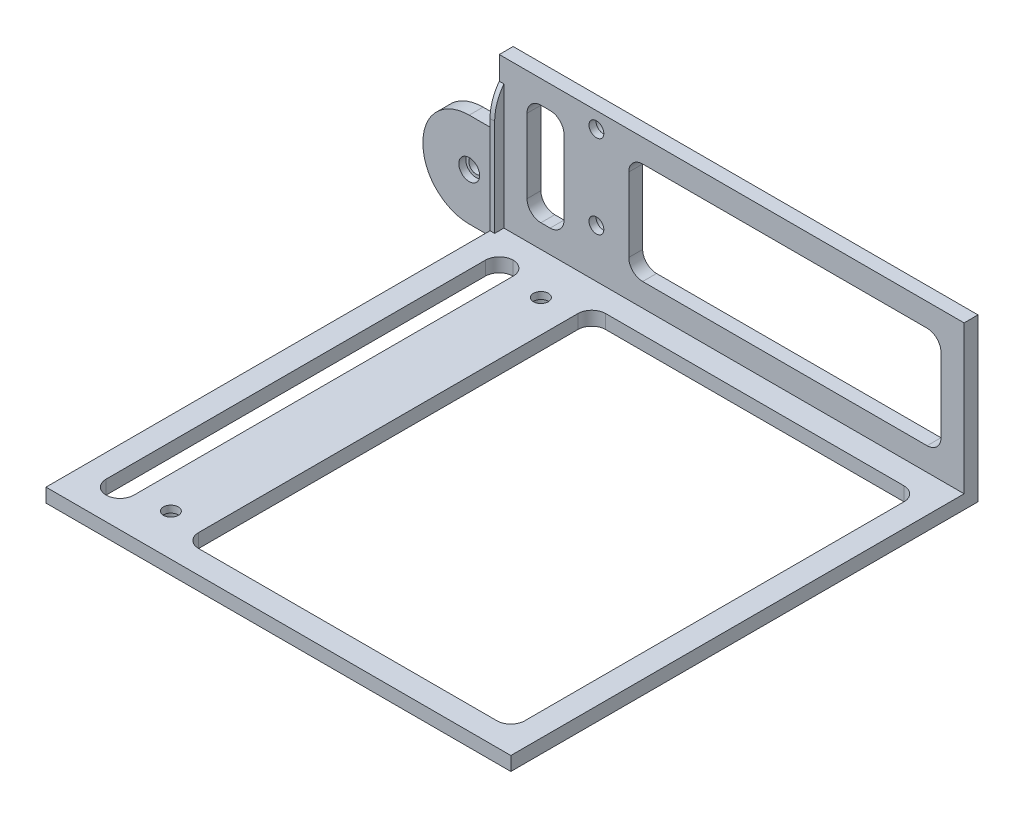
SolidWorks part; units mm, degrees
ref_plane "Front Plane" through (0, 0, 0) normal (0, 0, 1) x (1, 0, 0)
ref_plane "Top Plane" through (0, 0, 0) normal (0, 1, 0) x (1, 0, 0)
ref_plane "Right Plane" through (0, 0, 0) normal (1, 0, 0) x (0, 0, -1)
sketch "Sketch1" plane through (0, 0, 0) normal (0, 0, 1) x (1, 0, 0)
  line L1 (0, 0) -> (117, 0)
  line L2 (0, 0) -> (0, 35)
  line L3 (0, 35) -> (117, 35)
  line L4 (117, 0) -> (117, 35)
  line L5 (16.5, 30) -> (17.5, 30)
  line L6 (16.5, 30) -> (16.5, 3)
  line L7 (16.5, 3) -> (17.5, 3)
  line L8 (17.5, 30) -> (17.5, 3)
  line L9 (0, 0) -> (117, 0)
  line L10 (0, 0) -> (0, 3)
  line L11 (0, 3) -> (117, 3)
  line L12 (117, 0) -> (117, 3)
  circle A0 centre (10, 10.2) radius 1.6
  circle A2 centre (37.5, 13.5) radius 1.6
  circle A3 centre (37.5, 31.5) radius 1.6
  dimension "D3" = 10.2
  dimension "D4" = 3.2
  dimension "D6" = 1
  dimension "D7" = 3
  dimension "D8" = 5
  dimension "D10" = 13.5
  dimension "D11" = 3.2
  dimension "D12" = 3.2
  dimension "D1" = 117
  dimension "D2" = 35
  dimension "D5" = 10
  dimension "D9" = 99.5
  dimension "D13" = 20
  dimension "D14" = 20
  dimension "D15" = 18
  dimension "D16" = 3
extrude "Boss-Extrude1" add sketch "Sketch1" along normal blind 3 contours L2 L11 L6 L5 L8 L4 L3 A3 A2 A0 | L11 L2 L1 L4 L7 | L6 L7 L8 L5 region at (58.5, 1.5, 0) region at (59.0005, 19.0222, 0)
extrude "Boss-Extrude2" add sketch "Sketch1<3>" along normal blind 5 contours L6 L7 L8 L5
sketch "Sketch1<3>" plane through (0, 0, 0) normal (0, 0, 1) x (1, 0, 0) same geometry as "Sketch1"
extrude "Boss-Extrude3" add sketch "Sketch1<7>" along normal blind 101 contours L11 L2 L1 L4 L7 region at (58.5, 1.5, 0)
sketch "Sketch1<7>" plane through (0, 0, 0) normal (0, 0, 1) x (1, 0, 0) same geometry as "Sketch1"
sketch "Sketch2" plane through (0, 0, 0) normal (0, 0, -1) x (-1, 0, 0)
  circle A0 centre (-37.5, 31.5) radius 2.25
  circle A1 centre (-37.5, 13.5) radius 2.25
  dimension "D1" = 4.5
  dimension "D2" = 4.5
extrude "Cut-Extrude1" cut sketch "Sketch2" against normal blind 1.5
sketch "Sketch4" plane through (0, 0, 3) normal (0, 0, 1) x (1, 0, 0)
  circle A0 centre (10, 10.2) radius 2.25
  dimension "D1" = 4.5
extrude "Cut-Extrude2" cut sketch "Sketch4" against normal blind 1.5
sketch "Sketch5" plane through (0, 3, 0) normal (0, 1, 0) x (1, 0, 0)
  line L0 (117, -3) -> (17.5, -3) construction
  line L1 (17.5, -5) -> (17.5, -3) construction
  circle A0 centre (34.5, -12) radius 1.6
  circle A1 centre (34.5, -92) radius 1.6
  dimension "D1" = 9
  dimension "D2" = 3.2
  dimension "D4" = 3.2
  dimension "D3" = 17
  dimension "D5" = 80
  dimension "D6" = 17
extrude "Cut-Extrude3" cut sketch "Sketch5" against normal blind 3
sketch "Sketch6" plane through (0, 0, 0) normal (0, -1, 0) x (1, 0, 0)
  circle A0 centre (34.5, 92) radius 2.25
  circle A1 centre (34.5, 12) radius 2.25
  dimension "D1" = 4.5
  dimension "D2" = 4.5
extrude "Cut-Extrude4" cut sketch "Sketch6" against normal blind 1.5
sketch "Sketch7" plane through (0, 3, 0) normal (0, 1, 0) x (1, 0, 0)
  line L1 (0, -101) -> (16.5, -101)
  line L2 (0, -101) -> (0, -3)
  line L3 (0, -3) -> (16.5, -3)
  line L4 (16.5, -101) -> (16.5, -3)
extrude "Cut-Extrude5" cut sketch "Sketch7" against normal blind 3
sketch "Sketch8" plane through (0, 0, 3) normal (0, 0, 1) x (1, 0, 0)
  line L0 (16.5, 0) -> (16.5, 30) construction
  line L1 (16.5, 20.4) -> (0, 20.4)
  line L2 (16.5, 20.4) -> (16.5, 35)
  line L3 (16.5, 35) -> (0, 35)
  line L4 (0, 20.4) -> (0, 35)
  circle A0 centre (10, 10.2) radius 2.25 construction
  dimension "D1" = 10.2
extrude "Cut-Extrude6" cut sketch "Sketch8" against normal blind 3
fillet "Fillet1" radius 10 1 edges at (0, 20.4, 1.5)
fillet "Fillet2" radius 10 1 edges at (0, 0, 1.5)
fillet "Fillet3" radius 10 1 edges at (17, 30, 5)
sketch "Sketch9" plane through (0, 0, 3) normal (0, 0, 1) x (1, 0, 0)
  line L0 (16.5, 35) -> (117, 35) construction
  line L1 (44.5, 30) -> (112, 30)
  line L2 (44.5, 30) -> (44.5, 8)
  line L3 (44.5, 8) -> (112, 8)
  line L4 (112, 30) -> (112, 8)
  line L5 (117, 3) -> (117, 35) construction
  line L6 (117, 3) -> (17.5, 3) construction
  line L7 (16.5, 35) -> (117, 35) construction
  line L8 (22.5, 30) -> (30.5, 30)
  line L9 (22.5, 30) -> (22.5, 8)
  line L10 (22.5, 8) -> (30.5, 8)
  line L11 (30.5, 30) -> (30.5, 8)
  line L12 (17.5, 3) -> (17.5, 30) construction
  circle A0 centre (37.5, 13.5) radius 1.6 construction
  circle A1 centre (37.5, 31.5) radius 1.6 construction
  dimension "D1" = 5
  dimension "D2" = 5
  dimension "D3" = 5
  dimension "D4" = 7
  dimension "D5" = 5
  dimension "D6" = 5
  dimension "D7" = 7
  dimension "D8" = 5
extrude "Cut-Extrude7" cut sketch "Sketch9" against normal blind 10
fillet "Fillet4" radius 3 8 edges at (44.5, 30, 1.5) (44.5, 8, 1.5) (112, 8, 1.5) (112, 30, 1.5) (22.5, 8, 1.5) (30.5, 8, 1.5) (22.5, 30, 1.5) (30.5, 30, 1.5)
sketch "Sketch10" plane through (0, 3, 0) normal (0, 1, 0) x (1, 0, 0)
  line L0 (117, -3) -> (17.5, -3) construction
  line L1 (41.5, -8) -> (112, -8)
  line L2 (41.5, -8) -> (41.5, -96)
  line L3 (41.5, -96) -> (112, -96)
  line L4 (112, -8) -> (112, -96)
  line L5 (21.5, -8) -> (27.5, -8)
  line L6 (21.5, -8) -> (21.5, -96)
  line L7 (21.5, -96) -> (27.5, -96)
  line L8 (27.5, -8) -> (27.5, -96)
  line L9 (117, -101) -> (117, -3) construction
  line L10 (16.5, -101) -> (117, -101) construction
  line L11 (16.5, -101) -> (16.5, -5) construction
  circle A0 centre (34.5, -12) radius 1.6 construction
  dimension "D7" = 7
  dimension "D1" = 5
  dimension "D2" = 5
  dimension "D3" = 5
  dimension "D4" = 7
  dimension "D5" = 5
  dimension "D6" = 5
  dimension "D8" = 5
extrude "Cut-Extrude8" cut sketch "Sketch10" against normal blind 10
fillet "Fillet5" radius 3 8 edges at (21.5, 1.5, 8) (27.5, 1.5, 8) (21.5, 1.5, 96) (27.5, 1.5, 96) (41.5, 1.5, 96) (112, 1.5, 96) (41.5, 1.5, 8) (112, 1.5, 8)
